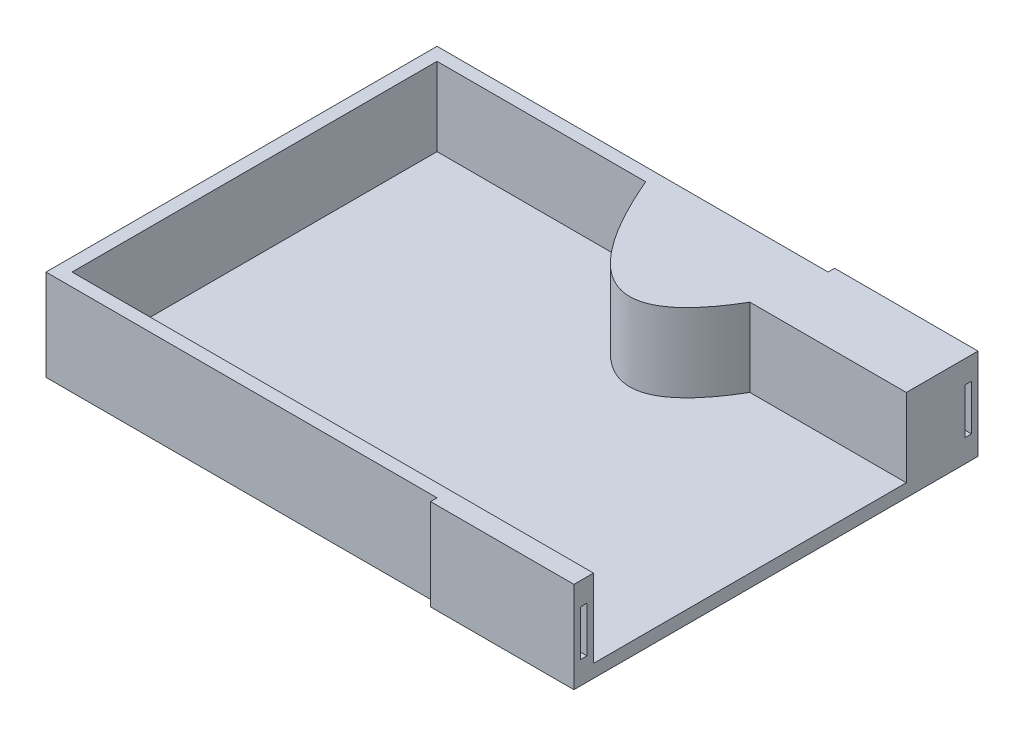
SolidWorks part; units mm, degrees
ref_plane "Alzado" through (0, 0, 0) normal (0, 0, 1) x (1, 0, 0)
ref_plane "Planta" through (0, 0, 0) normal (0, 1, 0) x (1, 0, 0)
ref_plane "Vista lateral" through (0, 0, 0) normal (1, 0, 0) x (0, 0, -1)
sketch "Croquis2" plane through (0, 0, 0) normal (0, 1, 0) x (1, 0, 0)
  line L0 (-200, 70) -> (200, 70)
  line L1 (-200, 70) -> (-200, -70)
  line L2 (-200, -70) -> (200, -70)
  line L3 (200, 70) -> (200, -70)
  line L4 (0, 70) -> (60, 70)
  line L5 (0, 70) -> (0, -70)
  line L6 (0, -70) -> (60, -70)
  line L7 (60, 70) -> (60, -70)
  line L8 (200, 70) -> (120, 70)
  line L9 (200, 70) -> (200, 50)
  line L10 (200, 50) -> (120, 50)
  line L11 (0, 70) -> (-60, 70)
  line L12 (0, 70) -> (0, 50)
  line L13 (0, 50) -> (-60, 50)
  line L14 (-60, 60.1561) -> (-60, 50)
  spline S0 degree 2 poles (60, 70) (89.7639, -0.5628) (120, 50) knots 0 0 0 1 1 1
  spline S1 degree 2 poles (-120, 70) (-89.7132, -0.7337) (-60, 50) knots 0 0 0 1 1 1
  point P14 (99.6856, 29.6804)
  point P15 (60, 70)
  point P16 (120, 50)
  point P18 (-120, 70)
  point P19 (-60, 50)
  point P20 (-79.8536, 29.6804)
extrude "Saliente-Extruir5" add sketch "Croquis2" along normal blind 35 contours L0 S1 L13 L5 region at (-64.087, 0, -55.7743)
extrude "Saliente-Extruir6" add sketch "Croquis2<6>" along normal blind 5 contours S1 L0 L1 L2 L5 L13 region at (-104.3301, 0, 6.7248)
sketch "Croquis2<6>" plane through (0, 0, 0) normal (0, 1, 0) x (1, 0, 0) same geometry as "Croquis2"
sketch "Croquis7" plane through (0, 0, 70) normal (0, 0, 1) x (1, 0, 0)
  line L1 (-200, 0) -> (0, 0)
  line L2 (-200, 0) -> (-200, 35)
  line L3 (-200, 35) -> (0, 35)
  line L4 (0, 0) -> (0, 35)
  dimension "D1" = 35
sketch "Croquis8" plane through (0, 0, -70) normal (0, 0, -1) x (-1, 0, 0)
  line L1 (200, 0) -> (0, 0)
  line L2 (200, 0) -> (200, 35)
  line L3 (200, 35) -> (0, 35)
  line L4 (0, 0) -> (0, 35)
extrude "Saliente-Extruir8" add sketch "Croquis8" along normal blind 5
extrude "Saliente-Extruir9" add sketch "Croquis7" along normal blind 5
sketch "Croquis10" plane through (-200, 0, 0) normal (-1, 0, 0) x (0, 0, 1)
  line L1 (-75, 0) -> (75, 0)
  line L2 (-75, 0) -> (-75, 35)
  line L3 (-75, 35) -> (75, 35)
  line L4 (75, 0) -> (75, 35)
extrude "Saliente-Extruir10" add sketch "Croquis10" along normal blind 5
sketch "Croquis11" plane through (0, 0, 75) normal (0, 0, 1) x (1, 0, 0)
  line L0 (0, 0) -> (0, 35) construction
  line L1 (0, 26.25) -> (-50, 26.25)
  line L2 (0, 26.25) -> (0, 8.75)
  line L3 (0, 8.75) -> (-50, 8.75)
  line L4 (-50, 26.25) -> (-50, 8.75)
  line L9 (0, 35) -> (-205, 35) construction
  dimension "D1" = 50
  dimension "D2" = 8.75
  dimension "D3" = 17.5
extrude "Cortar-Extruir1" cut sketch "Croquis11" against normal blind 2.5
sketch "Croquis12" plane through (0, 0, -75) normal (0, 0, -1) x (-1, 0, 0)
  line L0 (0, 35) -> (0, 0) construction
  line L1 (0, 26.25) -> (50, 26.25)
  line L2 (0, 26.25) -> (0, 8.75)
  line L3 (0, 8.75) -> (50, 8.75)
  line L4 (50, 26.25) -> (50, 8.75)
  line L5 (0, 0) -> (205, 0) construction
  dimension "D1" = 17.5
  dimension "D2" = 8.75
  dimension "D3" = 50
extrude "Cortar-Extruir2" cut sketch "Croquis12" against normal blind 2.5
sketch "Croquis13" plane through (0, 0, 75) normal (0, 0, 1) x (1, 0, 0)
  line L0 (0, 35) -> (-205, 35) construction
  line L1 (0, 0) -> (-55, 0)
  line L2 (0, 0) -> (0, 35)
  line L3 (0, 35) -> (-55, 35)
  line L4 (-55, 0) -> (-55, 35)
  dimension "D1" = 55
extrude "Saliente-Extruir11" add sketch "Croquis13" along normal blind 2.5
sketch "Croquis14" plane through (0, 0, -75) normal (0, 0, -1) x (-1, 0, 0)
  line L0 (205, 35) -> (0, 35) construction
  line L1 (0, 0) -> (55, 0)
  line L2 (0, 0) -> (0, 35)
  line L3 (0, 35) -> (55, 35)
  line L4 (55, 0) -> (55, 35)
  dimension "D1" = 55
extrude "Saliente-Extruir12" add sketch "Croquis14" along normal blind 2.5
sketch "Croquis15" plane through (0, 35, 0) normal (0, 1, 0) x (1, 0, 0)
  line L3 (-114.3779, 70) -> (-5, 70)
  line L4 (-5, 70) -> (-5, 55)
  line L5 (-5, 55) -> (-62.9096, 55)
  parabola Q1 (-120, 70) -> (-60, 50) focus (-84.886, 36.1958) apex (-84.8511, 28.8101) construction
  parabola Q2 (-120, 70) -> (-60, 50) focus (-84.886, 36.1958) apex (-84.8511, 28.8101) construction
  spline S4 degree 2 poles (-62.9096, 55) (-63.4663, 54.0216) (-64.4012, 52.3723) (-65.104, 51.1559) (-66.3439, 49.0845) (-69.3284, 44.5175) (-74.1123, 38.8128) (-78.5001, 35.5111) (-81.3049, 34.2924) (-83.3962, 33.8238) (-85.4337, 33.7921) (-88.0818, 34.2944) (-92.2861, 36.3652) (-99.2052, 42.5855) (-103.7996, 49.4252) knots -0.031024 -0.031024 -0.031024 -0.006934 0.009126 0.025186 0.065336 0.161696 0.290176 0.386536 0.450776 0.515016 0.579255 0.675615 0.804095 0.996815 0.996815 0.996815
  spline S5 degree 1 poles (-103.7996, 49.4252) (-114.3779, 70) knots 0.005992 0.005992 0.501862 0.501862
  point P7 (-84.8511, 28.8101)
extrude "Cortar-Extruir3" cut sketch "Croquis15" against normal blind 40 from offset 5 offset against normal yes
